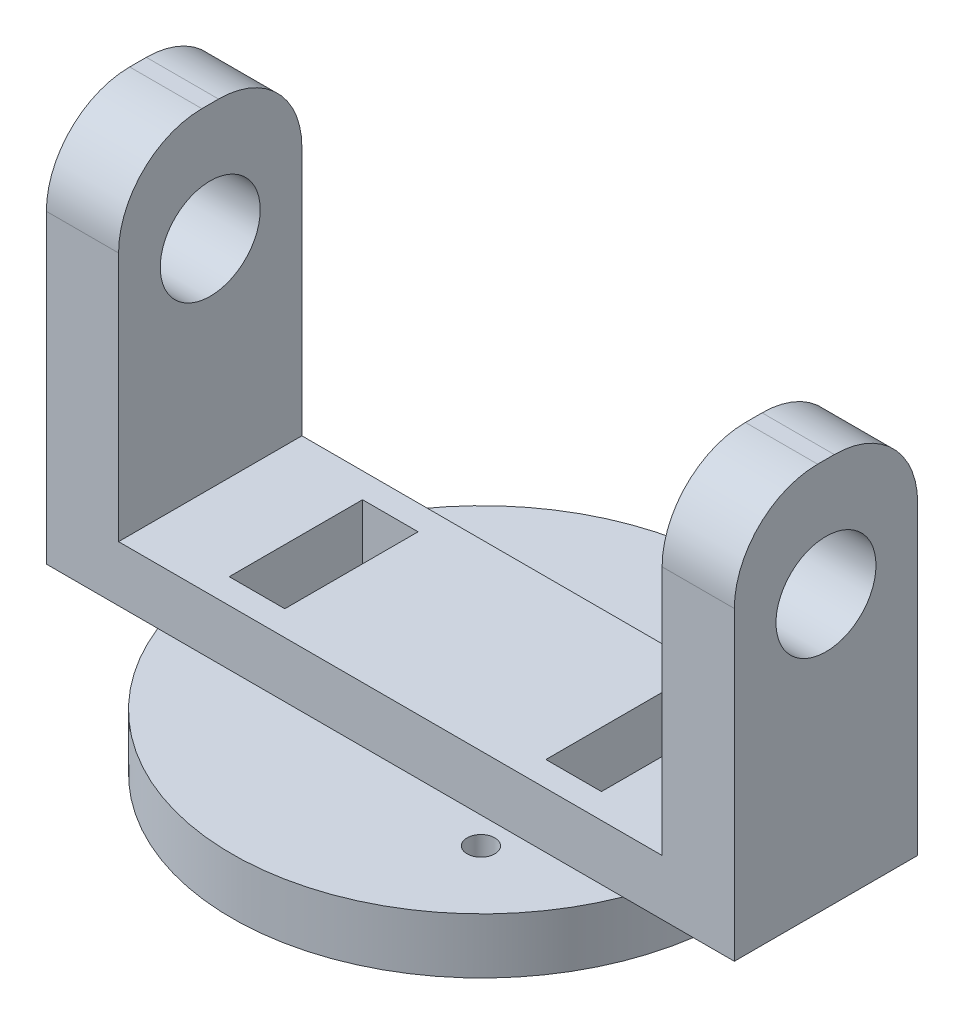
SolidWorks part; units mm, degrees
ref_plane "Front Plane" through (0, 0, 0) normal (0, 0, 1) x (1, 0, 0)
ref_plane "Top Plane" through (0, 0, 0) normal (0, 1, 0) x (1, 0, 0)
ref_plane "Right Plane" through (0, 0, 0) normal (1, 0, 0) x (0, 0, -1)
sketch "Sketch1" plane through (0, 0, 0) normal (0, 1, 0) x (1, 0, 0)
  line L1 (-61.92, 16.5) -> (61.92, 16.5)
  line L2 (-61.92, 16.5) -> (-61.92, -16.5)
  line L3 (-61.92, -16.5) -> (61.92, -16.5)
  line L4 (61.92, 16.5) -> (61.92, -16.5)
  point P4 (-61.92, 0)
  point P6 (0, 16.5)
  dimension "D1" = 33
  dimension "D2" = 123.84
extrude "Boss-Extrude1" add sketch "Sketch1" along normal blind 10 contours L1 L4 L3 L2
sketch "Sketch2" plane through (0, 10, 0) normal (0, 1, 0) x (1, 0, 0)
  line L0 (-61.92, -16.5) -> (61.92, -16.5) construction
  line L1 (-61.92, 16.5) -> (-48.92, 16.5)
  line L2 (-61.92, 16.5) -> (-61.92, -16.5)
  line L3 (-61.92, -16.5) -> (-48.92, -16.5)
  line L4 (-48.92, 16.5) -> (-48.92, -16.5)
  line L5 (-23.5, 7.472) -> (-23.5, -3.0599) construction
  line L11 (0, 0) -> (0, 32.5393) construction
  line L12 (48.92, 16.5) -> (48.92, -16.5)
  line L13 (61.92, -16.5) -> (48.92, -16.5)
  line L14 (61.92, 16.5) -> (61.92, -16.5)
  line L15 (61.92, 16.5) -> (48.92, 16.5)
  dimension "D1" = 25.42
  dimension "D2" = 23.5
extrude "Boss-Extrude2" add sketch "Sketch2" along normal blind 60
sketch "Sketch3" plane through (61.92, 0, 0) normal (1, 0, 0) x (0, 0, -1)
  line L6 (16.5, 0) -> (-16.5, 0) construction
  circle A0 centre (0, 49) radius 9
  point P3 (6.5836, 42.8636)
  dimension "D1" = 18
  dimension "D2" = 49
extrude "Cut-Extrude1" cut sketch "Sketch3" against normal through all
sketch "Sketch10" plane through (0, 0, 0) normal (0, -1, 0) x (1, 0, 0)
  circle A0 centre (0, 0) radius 45
  dimension "90" = 90
extrude "Boss-Extrude5" add sketch "Sketch10" along normal blind 10
sketch "Sketch9" plane through (0, 10, 0) normal (0, 1, 0) x (1, 0, 0)
  line L1 (-33.5, 12) -> (-23.5, 12)
  line L2 (-33.5, 12) -> (-33.5, -12)
  line L3 (-33.5, -12) -> (-23.5, -12)
  line L4 (-23.5, 12) -> (-23.5, -12)
  line L6 (0, 0) -> (0, 22.2113) construction
  line L7 (23.5, 12) -> (23.5, -12)
  line L8 (33.5, -12) -> (23.5, -12)
  line L9 (33.5, 12) -> (33.5, -12)
  line L10 (33.5, 12) -> (23.5, 12)
  circle A0 centre (0, 0) radius 30 construction
  circle A1 centre (21.1187, -21.3073) radius 2.5
  circle A4 centre (21.3073, 21.1187) radius 2.5
  circle A5 centre (-21.1187, 21.3073) radius 2.5
  point P4 (-31.6316, 12)
  point P5 (-33.5, 12)
  point P8 (-23.5, 0)
  point P20 (-34.7298, 12)
  point P21 (32.2702, 12.2197)
  point P24 (35.262, 13.1915)
  point P25 (-23.4484, 12)
  dimension "D3" = 60
  dimension "D4" = 5
  dimension "D5" = 5
  dimension "D7" = 5
  dimension "D1" = 24
  dimension "D2" = 10
  dimension "D6" = 90
  dimension "D8" = 90
  dimension "D9" = 47
  dimension "D10" = 10
  dimension "D11" = 24
  dimension "D12" = 23.5
extrude "Cut-Extrude3" cut sketch "Sketch9" against normal through all
fillet "Fillet1" radius 15 4 edges at (-55.42, 70, -16.5) (-55.42, 70, 16.5) (55.42, 70, 16.5) (55.42, 70, -16.5)
